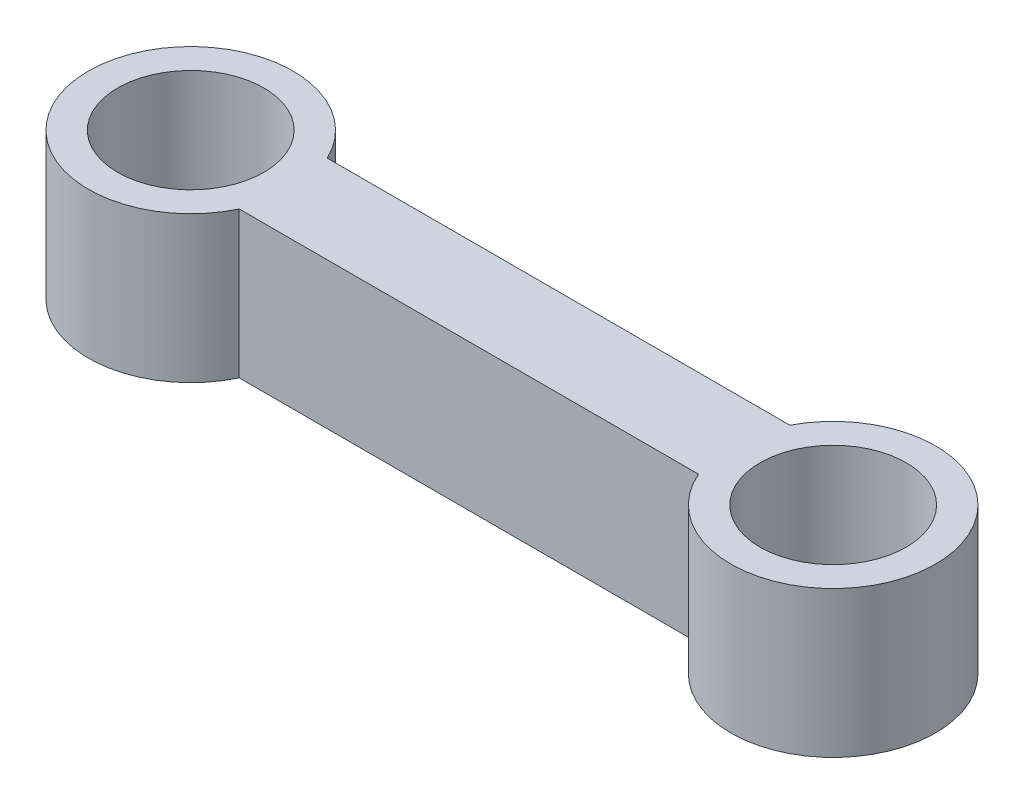
SolidWorks part; units mm, degrees
ref_plane "Plan de face" through (0, 0, 0) normal (0, 0, 1) x (1, 0, 0)
ref_plane "Plan de dessus" through (0, 0, 0) normal (0, 1, 0) x (1, 0, 0)
ref_plane "Plan de droite" through (0, 0, 0) normal (1, 0, 0) x (0, 0, -1)
sketch "Esquisse1" plane through (0, 0, 0) normal (0, 1, 0) x (1, 0, 0)
  line L0 (63.2001, 30.0955) -> (379.4018, 30.0955)
  line L1 (63.2001, -30.0955) -> (377.2097, -30.0955)
  circle A1 centre (0, 0) radius 70
  circle A2 centre (441.4546, -2.2999) radius 70
extrude "Boss.-Extru.2" add sketch "Esquisse1" along normal blind 100 contours A2 L0 A1 L1 | A1 | A2 region at (220.7488, 0, -0.0344) region at (0, 0, 0) region at (441.4546, 0, 2.2999)
sketch "Esquisse2" plane through (0, 100, 0) normal (0, 1, 0) x (1, 0, 0)
  circle A0 centre (0, 0) radius 50
  circle A1 centre (441.4546, -2.2999) radius 50
extrude "Enlèv. mat.-Extru.2" cut sketch "Esquisse2" against normal blind 95
